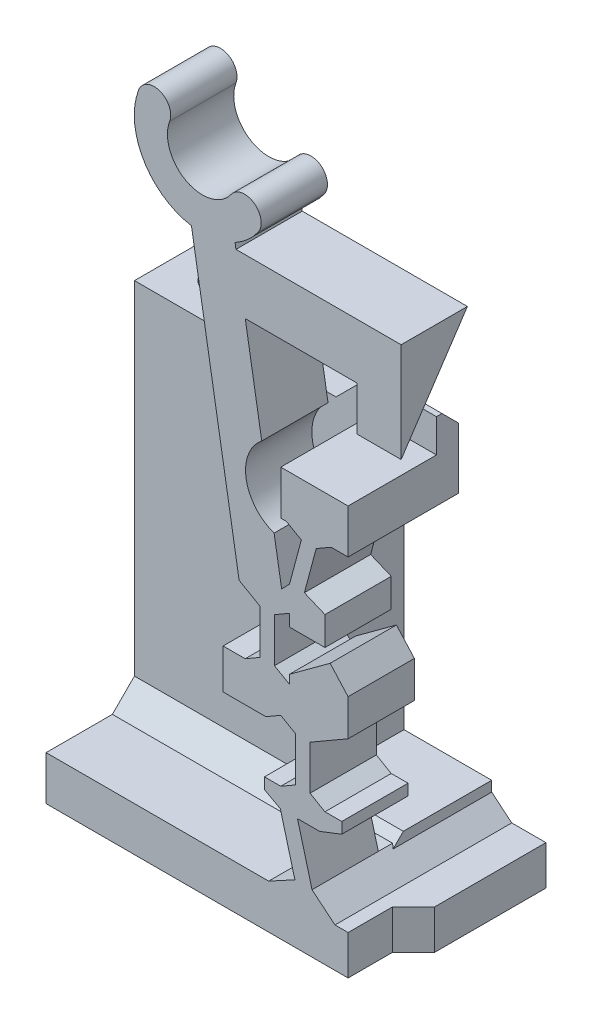
SolidWorks part; units mm, degrees
material "Nylon 6/12"
ref_plane "Front Plane" through (0, 0, 0) normal (0, 0, 1) x (1, 0, 0)
ref_plane "Top Plane" through (0, 0, 0) normal (0, 1, 0) x (1, 0, 0)
ref_plane "Right Plane" through (0, 0, 0) normal (1, 0, 0) x (0, 0, -1)
sketch "Sketch-SkeletonConfigUp" plane through (0, 0, 0) normal (0, 0, 1) x (1, 0, 0)
  line L0 (0, 0) -> (0, -50000) construction
  line L1 (0, 0) -> (4.5811, 6.2164) construction
  line L2 (9.8143, 13.3177) -> (4.5811, 13.945) construction
  line L3 (4.5811, 13.945) -> (2.9713, 10.4094) construction
  line L4 (2.9713, 10.4094) -> (4.5811, 6.2164) construction
  line L5 (4.5811, 13.945) -> (6.2429, 19.1409) construction
  line L6 (2.9713, 10.4094) -> (0.0405, 27.8193) construction
  line L7 (4.5811, 6.2164) -> (9.8143, 13.3177) construction
  line L8 (-587.3593, -797.0242) -> (9.8143, 13.3177) construction
  dimension "D2" = 7.7221
  dimension "D3" = 8.8212
  dimension "D4" = 5.2707
  dimension "D5" = 119.553
  dimension "D6" = 3.8848
  dimension "D7" = 5.4552
  dimension "D8" = 17.6549
  dimension "D9" = 4.4914
  dimension "D10" = 6.745
  dimension "D11" = 145.964
  dimension "D12" = 143.612
sketch "Sketch-SkeletonConfigDown" plane through (0, 0, 0) normal (0, 0, 1) x (1, 0, 0)
  line L0 (0, 0) -> (0, -50000) construction
  line L1 (0, 0) -> (4.5811, 6.2164) construction
  line L2 (9.8143, 13.3177) -> (4.5811, 13.945) construction
  line L3 (4.5811, 13.945) -> (6.1909, 10.4094) construction
  line L4 (6.1909, 10.4094) -> (4.5811, 6.2164) construction
  line L5 (4.5811, 13.945) -> (1.753, 18.6098) construction
  line L6 (6.1909, 10.4094) -> (-8.8652, 19.6294) construction
  line L7 (4.5811, 6.2164) -> (9.8143, 13.3177) construction
  line L8 (-589.9357, -800.5203) -> (9.8143, 13.3177) construction
  dimension "D2" = 7.7221
  dimension "D3" = 8.8212
  dimension "D4" = 5.2707
  dimension "D5" = 119.553
  dimension "D6" = 3.8848
  dimension "D7" = 5.4552
  dimension "D8" = 17.6549
  dimension "D9" = 4.4914
  dimension "D10" = 6.745
  dimension "D11" = 145.964
  dimension "D1" = 143.612
ref_plane "Plane-Cam Base" through (9.128, 0, 0) normal (1, 0, 0) x (0, 0, -1)
ref_plane "Plane-Down-to-Up Derailleur Clearance" through (6.628, 0, 0) normal (1, 0, 0) x (0, 0, -1)
ref_plane "Plane-Cam Cavity Roof" through (5.128, 0, 0) normal (1, 0, 0) x (0, 0, -1)
sketch "Sketch-SwitchBossUp" plane through (0, 0, 0) normal (0, 0, 1) x (1, 0, 0)
  line L0 (3.5811, 11.4759) -> (3.5811, 12.945) construction
  line L5 (5.5811, 12.5552) -> (5.5811, 11.263)
  line L7 (1.5115, 25.1048) -> (1.5536, 24.8548)
  line L8 (-0.4607, 24.7728) -> (1.6966, 11.9577)
  line L9 (2.9713, 10.4094) -> (0.0405, 27.8193) construction
  line L11 (0.1364, 21.2256) -> (2.1086, 21.5576) construction
  line L15 (6.628, -23.7286) -> (6.628, 23.7286) construction
  line L16 (2.9713, 10.4094) -> (4.5811, 6.2164) construction
  line L17 (3.5811, 12.945) -> (3.5811, 14.945) construction
  line L18 (5.5811, 12.945) -> (5.5811, 14.945) construction
  line L19 (4.2561, 13.945) -> (4.9061, 13.945) construction
  line L20 (3.5811, 14.945) -> (5.5811, 14.945) construction
  line L21 (3.5811, 12.945) -> (5.5811, 12.945) construction
  line L22 (4.5811, 12.945) -> (4.5811, 14.945) construction
  line L23 (4.5811, 6.2164) -> (8.5405, 7.1023) construction
  line L24 (1.9713, 9.4094) -> (1.9713, 11.4094) construction
  line L25 (3.9713, 9.4094) -> (3.9713, 11.4094) construction
  line L26 (3.9713, 9.4094) -> (1.9713, 9.4094) construction
  line L27 (1.9713, 11.4094) -> (3.9713, 11.4094) construction
  line L28 (3.5811, 7.2164) -> (5.5811, 7.2164) construction
  line L29 (3.5811, 7.2164) -> (3.5811, 5.2164) construction
  line L30 (5.5811, 7.2164) -> (5.5811, 5.2164) construction
  line L31 (3.5811, 5.2164) -> (5.5811, 5.2164) construction
  line L32 (4.9061, 6.2164) -> (4.2561, 6.2164) construction
  line L40 (3.2963, 10.4094) -> (2.6463, 10.4094) construction
  line L66 (0.0405, 27.8193) -> (0.0405, 50027.8193) construction
  line L75 (3.95, 3.937) -> (4.6085, 1.4797) construction
  line L76 (5.5811, 11.263) -> (5.5811, 12.5552) construction
  line L77 (5.5811, 7.6061) -> (6.628, 8.2105)
  line L80 (5.8152, 10.763) -> (6.628, 9.8603)
  line L81 (9.128, 1033.2419) -> (9.128, 20.0586) construction
  line L85 (6.9307, 9.5241) -> (8.5405, 7.7363) construction
  line L88 (5.7256, 17.3347) -> (6.628, 17.3347)
  line L92 (3.7762, 8.3129) -> (6.9307, 9.5241) construction
  line L98 (1.9713, 9.0197) -> (0.9713, 9.0197)
  line L99 (0.9713, 9.0197) -> (0.9713, 7.2164)
  line L100 (0.9713, 7.2164) -> (2.9061, 7.2164)
  line L101 (4.5811, 6.2164) -> (6.9307, 9.5241) construction
  line L103 (0.0405, 27.8193) -> (1.9448, 26.4638) construction
  line L104 (6.9307, 9.5241) -> (8.5405, 7.7363) construction
  line L107 (1.9713, 9.4094) -> (1.9713, 9.0197) construction
  line L109 (0.0405, 27.8193) -> (-2.1498, 28.6358) construction
  line L111 (6.628, 9.8603) -> (6.628, 8.2105)
  line L112 (6.628, 9.8603) -> (6.9307, 9.5241) construction
  line L113 (2.8424, 4.8267) -> (2.8424, 4.3267)
  line L114 (7.3693, 7.7363) -> (7.3563, 7.7363) construction
  line L121 (4.9967, -1.1226) -> (4.9967, 1.4797) construction
  line L122 (9.028, 22.3548) -> (9.028, 20.3548)
  line L127 (5.5811, 15.3347) -> (5.5811, 14.945) construction
  line L130 (6.0345, 0.6165) -> (6.628, 0.6165)
  line L132 (2.8424, 4.3267) -> (3.5618, 3.937)
  line L133 (2.9713, 10.4094) -> (6.1909, 10.4094) construction
  line L134 (4.5811, 10.4094) -> (4.5811, 13.945) construction
  line L135 (4.5811, 10.4094) -> (4.5811, 6.2164) construction
  line L137 (3.9713, 9.4094) -> (5.5811, 7.2164) construction
  line L139 (5.8152, 10.763) -> (3.9713, 9.4094)
  line L141 (4.2202, 1.4797) -> (3.0345, 0.8347)
  line L142 (3.0345, 0.8347) -> (3.0345, -1.1653)
  line L143 (9.128, 20.0586) -> (9.128, 18.3333) construction
  line L145 (9.128, 16.6071) -> (9.128, -49992.4167) construction
  line L147 (5.5811, 11.263) -> (5.5811, 12.5552) construction
  line L150 (3.0345, -1.1653) -> (6.628, -1.1653)
  line L151 (3.5618, 3.937) -> (4.3383, 3.937) construction
  line L152 (4.5126, 14.945) -> (3.9767, 12.945)
  line L153 (5.1855, 14.945) -> (4.6496, 12.945)
  line L157 (3.5811, 17.3347) -> (3.5811, 15.3347)
  line L158 (5.8605, 15.3347) -> (6.628, 15.3347)
  line L162 (3.2963, 11.4094) -> (3.2963, 9.4094)
  line L164 (2.6463, 11.4094) -> (2.6463, 9.4094)
  line L169 (4.2561, 7.2164) -> (4.2561, 5.2164)
  line L170 (4.9061, 5.2164) -> (4.9061, 7.2164)
  line L175 (4.2561, 7.2164) -> (3.5811, 7.6061)
  line L176 (4.9061, 7.2164) -> (5.5811, 7.6061)
  line L177 (5.5811, 7.2164) -> (5.5811, 7.6061) construction
  line L179 (4.2561, 5.2164) -> (3.5811, 4.8267)
  line L180 (3.5811, 5.2164) -> (3.5811, 4.8267) construction
  line L181 (3.5811, 4.8267) -> (2.8424, 4.8267)
  line L183 (4.9061, 5.2164) -> (5.5811, 4.8267)
  line L184 (5.5811, 5.2164) -> (5.5811, 4.8267) construction
  line L186 (9.128, -23.7286) -> (9.128, 23.7286) construction
  line L187 (2.6463, 9.4094) -> (1.9713, 9.0197)
  line L188 (3.2963, 9.4094) -> (3.9713, 9.0197)
  line L189 (3.2963, 11.4094) -> (3.9713, 11.7991)
  line L190 (2.6463, 11.4094) -> (1.6966, 11.9577)
  line L191 (3.9713, 11.4094) -> (3.9713, 11.7991) construction
  line L192 (3.9713, 11.7991) -> (3.9713, 11.263)
  line L193 (4.6496, 12.945) -> (5.5811, 12.5552)
  line L194 (3.9767, 12.945) -> (3.6203, 12.5779)
  line L195 (3.9713, 11.263) -> (5.5811, 11.263)
  line L196 (3.9713, 9.4094) -> (3.9713, 9.0197)
  line L197 (3.5811, 7.2164) -> (3.5811, 7.6061) construction
  line L199 (3.5811, 7.6061) -> (2.9061, 7.2164)
  line L201 (2.8424, 4.3267) -> (2.8424, 3.937) construction
  line L202 (2.8424, 3.937) -> (3.5618, 3.937) construction
  line L205 (3.0345, 1.4797) -> (3.0345, 0.8347) construction
  line L206 (4.9967, 1.4797) -> (6.0345, 0.6165)
  line L207 (9.128, 18.3333) -> (9.128, 16.6071) construction
  line L208 (6.628, -1.1653) -> (6.628, 0.6165)
  line L209 (9.128, 20.0586) -> (9.128, 16.6071) construction
  line L211 (4.9967, 1.4797) -> (4.3383, 3.937)
  line L212 (4.2202, 1.4797) -> (3.5618, 3.937)
  line L214 (4.5126, 14.945) -> (3.8375, 15.3347)
  line L215 (3.8375, 15.3347) -> (3.5811, 15.3347)
  line L216 (5.1855, 14.945) -> (5.8605, 15.3347)
  line L217 (5.5811, 12.945) -> (5.5811, 12.5552) construction
  line L218 (5.1855, 14.945) -> (5.1855, 15.3347) construction
  line L219 (5.8605, 15.3347) -> (3.8375, 15.3347) construction
  line L221 (9.028, 22.3548) -> (9.028, 24.8548)
  line L224 (3.5811, 17.3347) -> (5.7256, 17.3347)
  line L232 (6.628, 15.3347) -> (6.628, 17.3347)
  line L236 (1.5536, 24.8548) -> (9.028, 24.8548)
  line L240 (4.3383, 3.937) -> (5.3383, 3.937)
  line L241 (5.3383, 3.937) -> (6.3424, 4.3267)
  line L248 (7.028, 22.3548) -> (1.9744, 22.3548)
  line L249 (1.9744, 22.3548) -> (2.7198, 17.9273)
  line L250 (9.028, 20.3548) -> (7.028, 20.3548)
  line L251 (7.028, 20.3548) -> (7.028, 22.3548)
  line L252 (3.2801, 14.5986) -> (3.6203, 12.5779)
  line L253 (4.2672, 14.0291) -> (4.895, 13.8608) construction
  line L254 (4.9967, 1.4797) -> (4.2202, 1.4797) construction
  line L255 (4.2202, 1.4797) -> (3.0345, 1.4797) construction
  line L367 (5.5811, 4.8267) -> (6.3424, 4.8267)
  line L368 (6.3424, 4.8267) -> (6.3424, 4.3267)
  arc A0 (1.5115, 25.1048) -> (2.5558, 26.0289) centre (0.0405, 27.8193) ccw
  arc A1 (-0.4607, 24.7728) -> (-2.8525, 28.8978) centre (0.0405, 27.8193) cw
  arc A2 (-2.8525, 28.8978) -> (-1.447, 28.3738) centre (-2.1498, 28.6358) cw
  arc A3 (2.5558, 26.0289) -> (1.3338, 26.8987) centre (1.9448, 26.4638) ccw
  arc A4 (-1.447, 28.3738) -> (1.3338, 26.8987) centre (0.0405, 27.8193) ccw
  arc A5 (3.5811, 12.945) -> (3.5811, 14.945) centre (3.1778, 13.945) ccw construction
  arc A6 (5.5811, 12.945) -> (5.5811, 14.945) centre (5.9843, 13.945) cw construction
  arc A7 (2.5293, 9.921) -> (1.9713, 11.4094) centre (1.568, 10.4094) ccw construction
  arc A8 (3.9713, 11.4094) -> (3.9713, 9.4094) centre (4.3745, 10.4094) ccw construction
  arc A9 (3.5811, 7.2164) -> (3.5811, 5.2164) centre (3.1779, 6.2164) cw construction
  arc A10 (5.5811, 7.2164) -> (5.5811, 5.2164) centre (5.9844, 6.2164) ccw construction
  circle A28 centre (0.0405, 27.8193) radius 2.3375 construction
  arc A29 (1.9713, 9.4094) -> (2.5293, 9.921) centre (1.568, 10.4094) ccw construction
  arc A30 (3.2801, 14.5986) -> (2.7198, 17.9273) centre (3.9114, 16.4164) cw
  point P53 (4.5811, 13.945)
  point P63 (2.9713, 10.4094)
  point P93 (1.1225, 21.3916)
  dimension "D23" = 1.5875
  dimension "D24" = 0.75
  dimension "D2" = 2
  dimension "D5" = 2
  dimension "D8" = 42
  dimension "D16" = 42
  dimension "D27" = 120
  dimension "D28" = 120
  dimension "D29" = 120
  dimension "D30" = 120
  dimension "D31" = 120
  dimension "D32" = 120
  dimension "D33" = 120
  dimension "D34" = 120
  dimension "D17" = 0.5
  dimension "D21" = 2
  dimension "D38" = 2
  dimension "D39" = 0.5
  dimension "D40" = 60
  dimension "D41" = 1
  dimension "D42" = 45
  dimension "D43" = 120
  dimension "D10" = 15
  dimension "D25" = 15
  dimension "D26" = 120
  dimension "D35" = 120
  dimension "D20" = 3
  dimension "D48" = 2
  dimension "D82" = 1
  dimension "D83" = 3.5
  dimension "D14" = 2.5
  dimension "D15" = 0.25
  dimension "D7" = 2
  dimension "D9" = 2
  dimension "D6" = 0.65
  dimension "D12" = 0.75
extrude "Boss-Switch Body" add sketch "Sketch-SwitchBossUp" along normal blind 3
sketch "Sketch1" plane through (0, 0, 0) normal (0, 0, -1) x (-1, 0, 0)
  line L1 (-7.5811, -1.1653) -> (0.4122, -1.1653)
  line L2 (-7.5811, -1.1653) -> (-7.5811, 0.6165)
  line L4 (0.4122, -1.1653) -> (0.4122, 0.8347)
  line L5 (-3.5811, 18.8347) -> (-7.5811, 18.8347)
  line L10 (-7.5811, 18.8347) -> (-7.5811, 15.3347)
  line L11 (-4.2202, 1.4797) -> (-4.9967, 1.4797)
  line L12 (-7.5811, 15.3347) -> (-3.5811, 15.3347)
  line L13 (-4.2202, 1.4797) -> (-3.0345, 0.8347)
  line L14 (-3.5811, 15.3347) -> (-3.5811, 18.8347)
  line L20 (-4.3383, 3.937) -> (-4.9967, 1.4797) construction
  line L22 (-3.0345, -1.1653) -> (-6.628, -1.1653) construction
  line L23 (-3.0345, 0.8347) -> (0.4122, 0.8347)
  line L24 (-4.9967, 1.4797) -> (-6.0345, 0.6165)
  line L25 (-6.0345, 0.6165) -> (-7.5811, 0.6165)
  dimension "D1" = 3.5
extrude "Boss-Flange Width" add sketch "Sketch1" along normal blind 5
ref_plane "Plane-Sta2Sit Groove" through (0.0405, 0, 0) normal (1, 0, 0) x (0, 0, -1)
ref_plane "Plane-Cam Outer Surface" through (-12.0395, 0, 0) normal (1, 0, 0) x (0, 0, -1)
ref_plane "Plane-FlangeTop" through (-7.0395, 0, 0) normal (1, 0, 0) x (0, 0, -1)
sketch "Sketch2" plane through (-7.0395, 0, 0) normal (1, 0, 0) x (0, 0, -1)
  line L0 (5, 15.3347) -> (-3, 15.3347) construction
  line L1 (5, 17.3347) -> (1, 17.3347)
  line L2 (5, 17.3347) -> (5, 15.3347)
  line L3 (5, 15.3347) -> (1, 15.3347)
  line L4 (1, 17.3347) -> (1, 15.3347)
  line L5 (-3, -1.1653) -> (-3, 0.6165) construction
  line L11 (5, 0.8347) -> (-3, 0.8347)
  line L12 (5, 0.8347) -> (5, -1.1653)
  line L13 (5, -1.1653) -> (-3, -1.1653)
  line L14 (-3, 0.8347) -> (-3, -1.1653)
  line L15 (0, 10.4094) -> (0, 27.8193) construction
  line L17 (5, 0.6165) -> (5, -1.1653) construction
  line L18 (-3, 0.8347) -> (0, 0.8347) construction
  dimension "D1" = 1
  dimension "D2" = 2
extrude "Boss-Flange Height" add sketch "Sketch2" along normal up to surface (11.6675 mm away)
sketch "Sketch10" plane through (0, 15.3347, 0) normal (0, 1, 0) x (1, 0, 0)
  line L0 (9.128, -23.7286) -> (9.128, 23.7286) construction
  line L1 (7.5811, 5) -> (5.128, 5)
  line L2 (7.5811, 5) -> (7.5811, 2)
  line L3 (7.5811, 2) -> (5.128, 2)
  line L5 (4.628, 7) -> (4.628, 1) construction
  line L6 (3.5811, 1) -> (-7.0395, 1) construction
  line L8 (5.128, 5) -> (5.128, 2)
  dimension "D1" = 1
  dimension "D2" = 0.5
  dimension "D3" = 4.5
extrude "Cut-Up-To-Down Derailleur Clearance" cut sketch "Sketch10" along normal up to next
sketch "Sketch17" plane through (0, 15.3347, 0) normal (0, -1, 0) x (1, 0, 0)
  line L0 (5.128, -5) -> (-7.0395, -5)
  line L1 (5.128, -5) -> (-7.0395, -5) construction
  line L2 (-7.0395, -5) -> (-7.0395, -1)
  line L3 (-7.0395, -1) -> (5.128, -1)
  line L4 (5.128, -1) -> (5.128, -5)
  line L5 (-7.0395, -1) -> (-7.0395, -5) construction
extrude "Boss-Flange Support" add sketch "Sketch17" along normal up to surface (14.5 mm away) up to face at (-2.0025, 0.8347, -1)
sketch "Sketch-HolePositions" plane through (0, -1.1653, 0) normal (0, -1, 0) x (1, 0, 0)
  line L0 (-7.0395, -3) -> (7.5811, -3) construction
  line L1 (7.5811, -5) -> (-7.0395, -5) construction
  line L2 (7.5811, -5) -> (7.5811, 0) construction
  line L4 (-7.0395, -22.2167) -> (-7.0395, 22.2167) construction
  point P6 (-5.0395, -3)
  point P7 (-0.5395, -3)
  dimension "D1" = 2
  dimension "D2" = 4.5
  dimension "D3" = 2
sketch "Sketch6" plane through (0, -1.1653, 0) normal (0, -1, 0) x (-1, 0, 0)
  point P0 (5.0395, 3)
  point P3 (0.5395, 3)
hole_wizard "Tap Drill for M2x0.4 Tap1" positions "Sketch6" profile "Sketch5" hole size "M2x0.4" standard "ANSI Metric" end condition through all
sketch "Sketch5" plane through (-5.0395, -1.1653, -3) normal (1, 0, 0) x (0, 0, -1)
  line L0 (0, 0) -> (0, 30.5511)
  line L1 (0, 30.5511) -> (0.8, 30.5511)
  line L2 (0.8, 30.5511) -> (0.8, 0)
  line L5 (0.8, 0) -> (0, 0)
  line L11 (0, -6.35) -> (0, 107.95) construction
  dimension "Thru Hole Dia." = 1.6
  dimension "Thru Hole Depth" = 30.5511
sketch "Sketch9" plane through (0, -1.1653, 0) normal (0, -1, 0) x (1, 0, 0)
  point P0 (-5.0395, -3)
  point P3 (-0.5395, -3)
hole_wizard "M2 Clearance Hole2" positions "Sketch9" profile "Sketch8" hole size "M2" standard "ANSI Metric"
sketch "Sketch8" plane through (-5.0395, -1.1653, -3) normal (1, 0, 0) x (0, 0, -1)
  line L0 (0, 0) -> (0, 15.721)
  line L1 (0, 15.721) -> (1.2, 15)
  line L2 (1.2, 15) -> (1.2, 0)
  line L5 (1.2, 0) -> (0, 0)
  line L10 (0, 15.721) -> (-1.2, 15) construction
  line L11 (0, -6.35) -> (0, 107.95) construction
  dimension "Hole Dia." = 2.4
  dimension "Hole Depth" = 15
  dimension "Drill Angle" = 118
sketch "Sketch-Measurements for Derailleur Ramps" [suppressed] plane through (0, 0, 0) normal (0, 0, 1) x (1, 0, 0)
  line L0 (3.184, 15.1695) -> (2.4687, 19.4188)
  line L1 (2.8264, 17.2941) -> (1.8402, 17.1281)
  line L2 (2.9713, 10.4094) -> (0.0405, 27.8193) construction
  line L3 (1.8402, 17.1281) -> (-1.3081, 15.0016)
  line L4 (6.1909, 10.4094) -> (-8.8652, 19.6294) construction
  line L5 (1.8402, 17.1281) -> (2.6012, 12.6077)
  line L6 (2.6012, 12.6077) -> (-1.3081, 15.0016)
  line L7 (0.2661, 16.0649) -> (0.2661, 17.1281)
  line L8 (0.2661, 17.1281) -> (1.8402, 17.1281)
  line L9 (6.1909, 10.4094) -> (2.9713, 10.4094)
  line L10 (5.386, 8.3129) -> (3.7762, 8.3129)
  line L11 (2.6116, 18.5698) -> (1.5115, 25.1048) construction
  line L12 (6.1909, 10.4094) -> (4.5811, 6.2164) construction
  line L13 (4.5811, 8.3129) -> (4.5811, 8.7912)
  line L14 (4.5811, 6.2164) -> (5.386, 8.3129)
  line L15 (2.9713, 10.4094) -> (4.5811, 6.2164) construction
  line L16 (3.7762, 8.3129) -> (4.5811, 6.2164)
  line L17 (5.386, 8.3129) -> (5.386, 8.7912)
  dimension "D1" = 1.5742
  dimension "D2" = 0.8049
ref_plane "Plane1" through (0, 7.1023, 0) normal (0, 1, 0) x (1, 0, 0)
ref_plane "Plane-Cantilever Cut" [suppressed] through (7.0848, 8.5204, -1.9058) normal (-0.6301, -0.7578, 0.1695) x (-0.7765, 0.6151, -0.1368)
sketch "Sketch14" [suppressed] plane through (7.0848, 8.5204, -1.9058) normal (-0.6301, -0.7578, 0.1695) x (-0.7765, 0.6151, -0.1368)
  line L0 (2.3023, -1.6911) -> (-0.3551, -1.6911)
  line L2 (2.3023, -4.3362) -> (2.3023, -1.6911)
  line L3 (-0.3551, -1.6911) -> (-0.3551, -4.4608)
  line L5 (-0.3551, -4.4608) -> (1.0087, -5.0843)
  line L6 (1.0087, -5.0843) -> (2.3023, -4.3362)
extrude "Cut-Down-to-Up Cantilever Slope" [suppressed] cut sketch "Sketch14" against normal up to next
ref_plane "Plane-Symmetry Plane" through (0, 0, 1.5) normal (0, 0, 1) x (1, 0, 0)
sketch "Sketch-Cable Center Point" plane through (0, 0, 1.5) normal (0, 0, 1) x (1, 0, 0)
  line L0 (0.0405, 27.8193) -> (0.1722, 27.0366)
  line L1 (2.9713, 10.4094) -> (0.0405, 27.8193) construction
  point P0 (0.0405, 27.8193)
  dimension "D1" = 0.7937
chamfer "Chamfer-Flange Support" distance 1.5 angle 45 1 edges at (3.5811, 17.3347, -3)
chamfer "Chamfer-Flange Support 2" distance 1.5 angle 45 2 edges at (5.128, 17.0847, -2) (5.128, 15.3347, -1.5)
chamfer "Chamfer-Flange Support 3" distance 1 angle 45 1 edges at (-2.0025, 0.8347, -1)
chamfer "Chamfer7" [suppressed] distance 1 angle 45
sketch "Sketch23" plane through (0, 0, -1) normal (0, 0, 1) x (1, 0, 0)
  line L0 (5.128, 1.8347) -> (1.1605, 1.8347)
  line L1 (-7.0395, 1.8347) -> (5.128, 1.8347) construction
  line L2 (1.1605, 1.8347) -> (1.1605, 13.8347)
  line L3 (1.1605, 13.8347) -> (5.128, 13.8347)
  line L4 (5.128, 13.8347) -> (5.128, 1.8347)
  line L5 (0.6605, -1.1653) -> (0.6605, 13.8347) construction
  dimension "D1" = 0.5
extrude "Cut-Gap for Printing" cut sketch "Sketch23" against normal through all
sketch "Sketch25" plane through (0, 0, 0) normal (0, 0, 1) x (1, 0, 0)
  line L0 (6.628, 15.3347) -> (7.5811, 15.3347)
  line L1 (7.5811, 15.3347) -> (7.5811, 18.8347)
  line L2 (7.5811, 18.8347) -> (6.628, 18.8347)
  line L3 (6.628, -23.7286) -> (6.628, 23.7286) construction
  line L4 (7.5811, 18.8347) -> (3.5811, 18.8347) construction
  line L5 (6.628, 18.8347) -> (6.628, 15.3347)
  line L6 (7.5811, 18.8347) -> (7.5811, 15.3347) construction
extrude "Cut-Derailleur Clearance" cut sketch "Sketch25" against normal through all
chamfer "Chamfer8" distance 1 angle 45 1 edges at (6.628, -0.2744, 0)
ref_plane "Plane2" through (-3.0866, 5.589, 8.3835) normal (0.2929, -0.5304, -0.7956) x (-0.9561, -0.1625, -0.2437)
sketch "Sketch26" plane through (-3.0866, 5.589, 8.3835) normal (0.2929, -0.5304, -0.7956) x (-0.9561, -0.1625, -0.2437)
  line L0 (-7.553, 20.6804) -> (-7.553, 14.9094)
  line L1 (-12.6703, 20.6804) -> (-5.5238, 20.6804) construction
  line L3 (-7.553, 14.9094) -> (-20.0302, 14.9094)
  line L4 (-20.0302, 14.9094) -> (-20.0302, 20.6804)
  line L5 (-20.0302, 20.6804) -> (-7.553, 20.6804)
extrude "Cut-Up-to-Down Cantilever Slope" cut sketch "Sketch26" along normal up to next
sketch "Sketch27" plane through (5.128, 0, 0) normal (1, 0, 0) x (0, 0, -1)
  line L0 (3.5, 18.8347) -> (3.5, 13.8347) construction
  line L1 (2.5, 18.8347) -> (5, 18.8347)
  line L2 (2.5, 18.8347) -> (2.5, 13.8347)
  line L3 (2.5, 13.8347) -> (5, 13.8347)
  line L4 (5, 18.8347) -> (5, 13.8347)
  dimension "D1" = 1
extrude "Cut-Wide Derailleur Clearance" cut sketch "Sketch27" against normal blind 4 and the other way through all
chamfer "Chamfer9" distance 1.25 angle 45 1 edges at (4.8545, 18.8347, -2.5)
sketch "Sketch28" plane through (0, 0, -1) normal (0, 0, 1) x (1, 0, 0)
  line L0 (3.5811, 18.8347) -> (6.628, 18.8347)
  line L1 (6.628, 18.8347) -> (6.628, 17.3347)
  line L2 (6.628, 17.3347) -> (3.5811, 17.3347)
  line L3 (3.5811, 17.3347) -> (3.5811, 18.8347)
extrude "Cut-Extrude1" cut sketch "Sketch28" along normal up to surface (1 mm away) up to face at (5.1045, 18.0847, 0)
equation "\"axle-diameter\"=2"
equation "\"switch-thickness\"=12"
equation "\"base-width\"=4.0"
equation "\"axle-bushing-radius\"=3"
equation "\"clearance\"= 0.25"
equation "\"arm-width\"=1.5"
equation "\"min-diameter\"=70"
equation "\"alpha\"=143.6120"
equation "\"gamma\"=119.5526"
equation "\"delta\"=145.9637"
equation "\"epsilon\"=6.7452"
equation "\"l_AB\"=8.8212"
equation "\"l_AC\"=4.4914"
equation "\"l_BD\"=5.2707"
equation "\"l_CD\"=3.8848"
equation "\"l_CE\"=17.6549"
equation "\"l_DF\"=5.4552"
equation "\"l_OA\"=7.7221"
equation "\"D2@Sketch-SkeletonConfigUp\" = \"l_OA\""
equation "\"D3@Sketch-SkeletonConfigUp\" = \"l_AB\""
equation "\"D4@Sketch-SkeletonConfigUp\" = \"l_BD\""
equation "\"D5@Sketch-SkeletonConfigUp\" = \"gamma\""
equation "\"D6@Sketch-SkeletonConfigUp\" = \"l_CD\""
equation "\"D7@Sketch-SkeletonConfigUp\" = \"l_DF\""
equation "\"D8@Sketch-SkeletonConfigUp\" = \"l_CE\""
equation "\"D9@Sketch-SkeletonConfigUp\" = \"l_AC\""
equation "\"D_groove\"=3.175"
equation "\"D7@Sketch-SkeletonConfigDown\" = \"l_DF\""
equation "\"D6@Sketch-SkeletonConfigDown\" = \"l_CD\""
equation "\"D2@Sketch-SkeletonConfigDown\" = \"l_OA\""
equation "\"D3@Sketch-SkeletonConfigDown\" = \"l_AB\""
equation "\"D9@Sketch-SkeletonConfigDown\" = \"l_AC\""
equation "\"D8@Sketch-SkeletonConfigDown\" = \"l_CE\""
equation "\"D5@Sketch-SkeletonConfigDown\" = \"gamma\""
equation "\"D4@Sketch-SkeletonConfigDown\" = \"l_BD\""
equation "\"D1@Sketch-SkeletonConfigDown\" = \"alpha\""
equation "\"hinge_length\"=1.5"
equation "\"hinge_depth\"=0.25"
equation "\"D10@Sketch-SkeletonConfigUp\"=\"epsilon\""
equation "\"D11@Sketch-SkeletonConfigUp\"=\"delta\""
equation "\"D12@Sketch-SkeletonConfigUp\"=\"alpha\""
equation "\"D11@Sketch-SkeletonConfigDown\"=\"delta\""
equation "\"D10@Sketch-SkeletonConfigDown\"=\"epsilon\""
equation "\"EE_dx\"=8.9056"
equation "\"EE_dy\"=8.1898"
equation "\"r_groove\"=\"D_groove\"/2"
equation "\"t_wall\"=25.4/16"
equation "\"width_lower\"=\"D_groove\"+\"t_wall\""
equation "\"cable_to_bottom\"=30.6257"
equation "\"switch_EE-up_base_dy\"=24"
equation "\"switch_EE-down_base_dy\"=16"
equation "\"D_axle\"=25.4/8"
equation "\"D_up_to_down\"=16"
equation "\"D_down_to_up\"=25"
equation "\"t_cam_base\"=7.5"
equation "\"D23@Sketch-SwitchBossUp\"=\"D_groove\"/2"
equation "\"D1@Sketch-Cable Center Point\"=\"D_groove\"/4"
